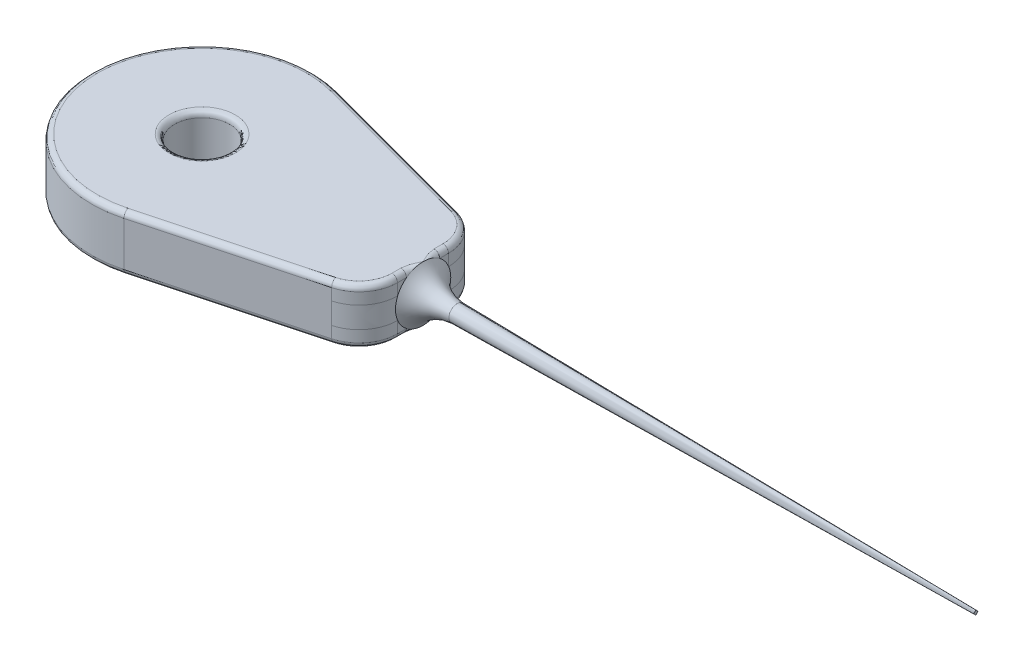
SolidWorks part; units mm, degrees
ref_plane "Front Plane" through (0, 0, 0) normal (0, 0, 1) x (1, 0, 0)
ref_plane "Top Plane" through (0, 0, 0) normal (0, 1, 0) x (1, 0, 0)
ref_plane "Right Plane" through (0, 0, 0) normal (1, 0, 0) x (0, 0, -1)
sketch "Sketch1" plane through (0, 0, 0) normal (0, 1, 0) x (1, 0, 0)
  line L0 (-2369.7199, 0) -> (420.6127, 0) construction
  line L1 (25.8819, 96.5926) -> (200, 49.9378)
  line L2 (25.8819, -96.5926) -> (200, -49.9378)
  line L3 (200, 49.9378) -> (200, -49.9378)
  arc A0 (25.8819, 96.5926) -> (25.8819, -96.5926) centre (0, 0) ccw
  dimension "D1" = 200
  dimension "D2" = 200
  dimension "D3" = 30
extrude "Boss-Extrude1" add sketch "Sketch1" along normal mid plane 50
sketch "Sketch2" plane through (0, 25, 0) normal (0, 1, 0) x (1, 0, 0)
  circle A0 centre (0, 0) radius 25
  dimension "D1" = 50
extrude "Cut-Extrude1" cut sketch "Sketch2" against normal blind 40
sketch "Sketch3" plane through (200, 0, 0) normal (1, 0, 0) x (0, 0, -1)
  line L1 (-49.9378, 25) -> (49.9378, 25) construction
  circle A0 centre (0, 0) radius 25
extrude "Boss-Extrude2" add sketch "Sketch3" along normal blind 500
sketch "Sketch4" plane through (0, 0, 0) normal (0, 0, 1) x (1, 0, 0)
  line L0 (-94.7525, 0) -> (774.519, 0) construction
  line L1 (200, 25) -> (700, 25)
  line L2 (700, 25) -> (700, 2)
  line L3 (700, -25) -> (700, 25) construction
  arc A1 (200, 25) -> (230.6943, 7.5141) centre (231.7214, 45) ccw
  arc A2 (230.6943, 7.5141) -> (700, 2) centre (641.5547, 15001.8861) ccw
  dimension "D2" = 75
  dimension "D3" = 15000
  dimension "D1" = 2
  dimension "D4" = 20
revolve "Cut-Revolve1" cut sketch "Sketch4" angle 360 about L0
fillet "Fillet1" radius 35 2 edges at (200, 0, 49.9378) (200, 0, -49.9378)
fillet "Fillet2" radius 5 15 edges at (200, -25, -11.5407) (192.7674, -25, -44.388) (99.9703, -25, -76.7407) (-100, -25, 0) (99.9703, -25, 76.7407) (192.7674, -25, 44.388) (200, -25, 11.5407) (-100, 25, 0) (99.9703, 25, -76.7407) (192.7674, 25, -44.388) (200, 25, -11.5407) (200, 25, 11.5407) (192.7674, 25, 44.388) (99.9703, 25, 76.7407) (0, 25, 25)
